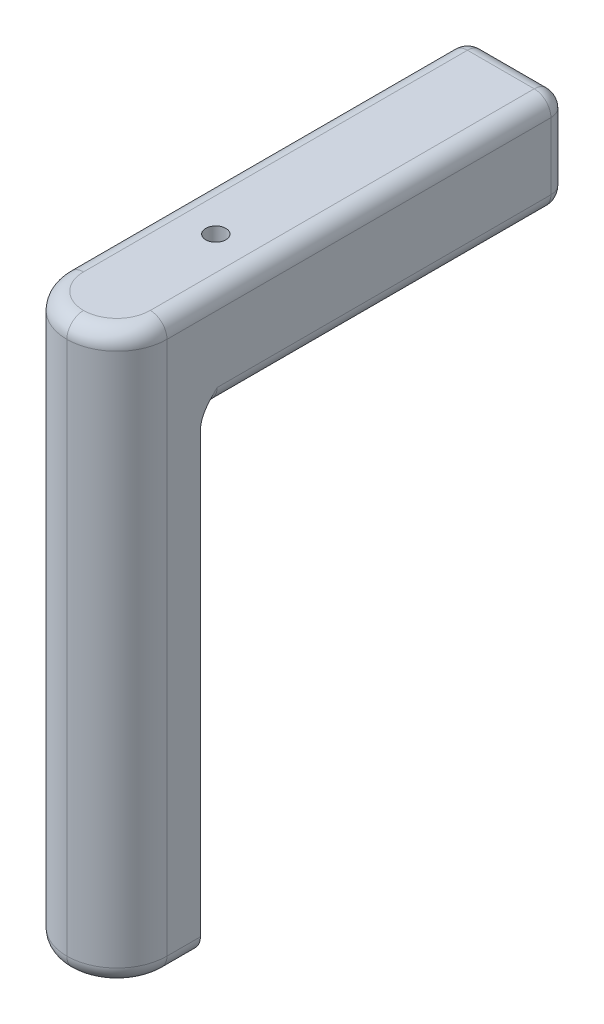
SolidWorks part; units mm, degrees
ref_plane "Front Plane" through (0, 0, 0) normal (0, 0, 1) x (1, 0, 0)
ref_plane "Top Plane" through (0, 0, 0) normal (0, 1, 0) x (1, 0, 0)
ref_plane "Right Plane" through (0, 0, 0) normal (1, 0, 0) x (0, 0, -1)
sketch "Sketch1" plane through (0, 0, 0) normal (0, 0, 1) x (1, 0, 0)
  line L0 (0, 0) -> (60, 0)
  line L1 (60, 0) -> (60, -60)
  line L2 (60, -60) -> (0, -60)
  line L3 (0, -60) -> (0, 0)
  dimension "D1" = 60
  dimension "D2" = 60
extrude "Boss-Extrude1" add sketch "Sketch1" along normal blind 270
sketch "Sketch2" plane through (0, -60, 0) normal (0, -1, 0) x (1, 0, 0)
  line L0 (0, 270) -> (60, 270)
  line L1 (60, 270) -> (60, 220)
  line L2 (60, 270) -> (60, 0) construction
  line L3 (60, 220) -> (0, 220)
  line L4 (0, 270) -> (0, 0) construction
  line L5 (0, 220) -> (0, 270)
  dimension "D1" = 50
extrude "Boss-Extrude2" add sketch "Sketch2" along normal blind 280
sketch "Sketch3" plane through (0, 0, 0) normal (0, 0, -1) x (-1, 0, 0)
  line L0 (0, -60) -> (-60, -60) construction
  line L1 (-60, -60) -> (-60, 0) construction
  circle A0 centre (-30, -30) radius 15
  dimension "D1" = 30
  dimension "D2" = 30
extrude "Cut-Extrude1" cut sketch "Sketch3" against normal blind 50 contours A0
sketch "Sketch4" plane through (0, 0, 220) normal (0, 0, -1) x (-1, 0, 0)
  line L0 (-60, -340) -> (-60, -60) construction
  line L1 (0, -340) -> (-60, -340) construction
  circle A0 centre (-30, -300) radius 27.5
  dimension "D1" = 30
  dimension "D2" = 40
extrude "Cut-Extrude2" cut sketch "Sketch4" against normal blind 25
fillet "Fillet1" radius 30 1 edges at (60, -170, 270) type face fillet first side face at (60, -133.3333, 163.3333) second side face at (30, -170, 270)
fillet "Fillet2" radius 30 1 edges at (0, -170, 270) type face fillet first side face at (15, -170, 270) second side face at (0, -133.3333, 163.3333)
fillet "Fillet3" radius 10 2 edges at (0, 0, 120) (60, 0, 120) type face fillet first side face at (0, -133.3333, 153.3333) first side face at (60, -133.3333, 153.3333) second side face at (30, 0, 152.4853)
fillet "Fillet4" radius 10 2 edges at (0, -35, 0) (60, -35, 0) type face fillet first side face at (0, -136.6667, 153.3333) first side face at (60, -136.6667, 153.3333) second side face at (15, -30, 0)
fillet "Fillet5" radius 10 1 edges at (30, -60, 0) type face fillet first side face at (15, -30, 0) second side face at (30, -60, 75.9763)
fillet "Fillet6" radius 10 1 edges at (30, -60, 220) type face fillet first side face at (2.5, -300, 220) second side face at (30, -60, 115)
fillet "Fillet7" radius 10 4 edges at (8.7868, -340, 261.2132) (51.2132, -340, 261.2132) (0, -340, 230) (60, -340, 230) type face fillet first side face at (60, -124.4258, 164.8723) first side face at (48.1066, -175, 258.1066) first side face at (11.8934, -175, 258.1066) first side face at (0, -124.4258, 164.8723) second side face at (30, -340, 240.4853)
sketch "Sketch5" plane through (0, -60, 0) normal (0, -1, 0) x (1, 0, 0)
  line L0 (50, 210) -> (10, 210) construction
  circle A0 centre (30, 180.76) radius 6
  dimension "D1" = 12
  dimension "D2" = 29.24
extrude "Cut-Extrude4" cut sketch "Sketch5" against normal through all contours A0
